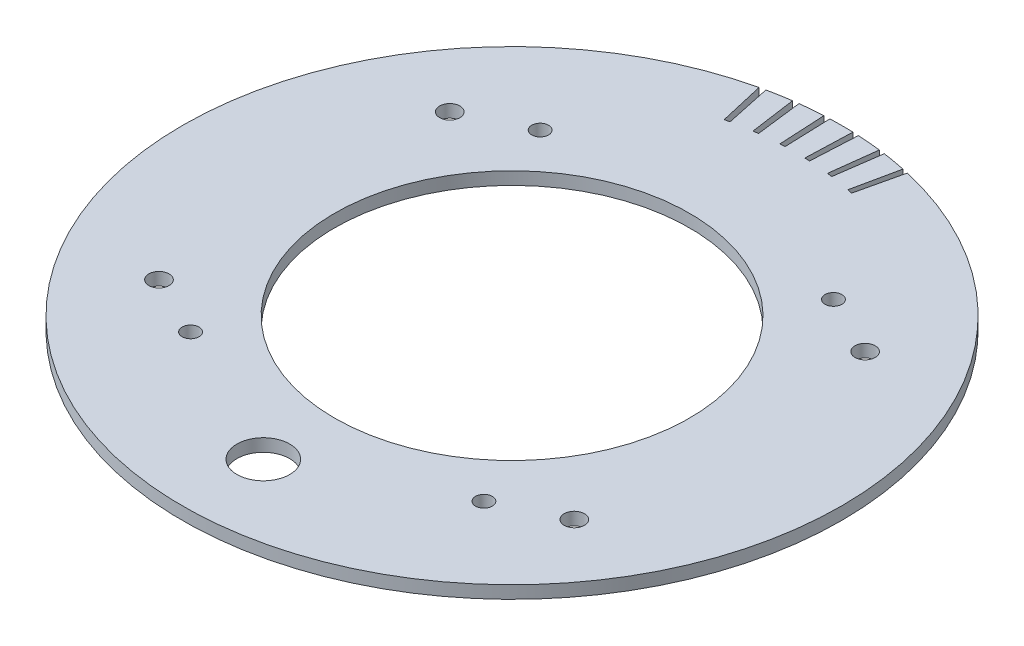
SolidWorks part; units mm, degrees
material "G10 Fiber Reinforced Plastic"
ref_plane "Front Plane" through (0, 0, 0) normal (0, 0, 1) x (1, 0, 0)
ref_plane "Top Plane" through (0, 0, 0) normal (0, 1, 0) x (1, 0, 0)
ref_plane "Right Plane" through (0, 0, 0) normal (1, 0, 0) x (0, 0, -1)
sketch "98mm - 6ID centering ring sketch" plane through (0, 0, 0) normal (0, 1, 0) x (1, 0, 0)
  line L0 (0, 0) -> (0, 50000) construction
  line L1 (0, 0) -> (50000, 0) construction
  line L2 (99.0091, 3.175) -> (56.4257, 3.175)
  line L3 (-99.0091, -3.175) -> (-56.4257, -3.175)
  line L4 (3.175, -99.0091) -> (3.175, -56.4257)
  line L5 (-3.175, 99.0091) -> (-3.175, 56.4257)
  line L7 (-56.4257, 3.175) -> (-99.0091, 3.175)
  line L8 (-3.175, -56.4257) -> (-3.175, -99.0091)
  line L9 (3.175, 56.4257) -> (3.175, 99.0091)
  line L11 (56.4257, -3.175) -> (99.0091, -3.175)
  circle A0 centre (0, 0) radius 99.06
  circle A1 centre (0, 0) radius 53.34
  arc A2 (-56.4257, 3.175) -> (-56.4257, -3.175) centre (0, 0) ccw
  arc A3 (-3.175, -56.4257) -> (3.175, -56.4257) centre (0, 0) ccw
  arc A4 (56.4257, -3.175) -> (56.4257, 3.175) centre (0, 0) ccw
  arc A5 (3.175, 56.4257) -> (-3.175, 56.4257) centre (0, 0) ccw
  dimension "D1" = 45.72
  dimension "D2" = 106.68
  dimension "D5" = 3.175
  dimension "D3" = 6.35
  dimension "D4" = 6.35
  dimension "D6" = 6.35
extrude "Centering Ring Extrude" add sketch "98mm - 6ID centering ring sketch" along normal blind 1.905 and the other way blind 1.905 contours L9 A5 L5 A0 L7 A2 L3 L8 A3 L4 L11 A4 L2 A1 | A4 L11 A0 L2 | A5 L9 A0 L5 | A2 L7 A0 L3 | A3 L8 A0 L4 region at (77.7641, 0, 0) region at (77.7174, 0, -5.9754) region at (0, 0, -77.7641) region at (0, 0, 77.7641) region at (-77.7641, 0, 0)
sketch "Sketch1" plane through (0, -1.905, 0) normal (0, -1, 0) x (1, 0, 0)
  line L0 (0, 0) -> (14.5226, 68.3236) construction
  line L1 (0, 0) -> (32.7926, -61.6739)
  line L2 (0, 0) -> (-55.0426, -43.004)
  line L3 (0, 0) -> (0, 69.85) construction
  circle A0 centre (0, 0) radius 69.85 construction
  circle A1 centre (32.7926, -61.6739) radius 3.175
  circle A2 centre (-55.0426, -43.004) radius 3.175
  dimension "D1" = 139.7
  dimension "D2" = 6.35
  dimension "D3" = 140
  dimension "D4" = 12
sketch "Sketch3" plane through (0, 1.905, 0) normal (0, 1, 0) x (1, 0, 0)
  line L0 (0, 0) -> (0, 99.06) construction
  line L1 (0, 0) -> (-22.2837, 96.5211)
  line L2 (0, 0) -> (-20.5957, 96.8953)
  circle A0 centre (0, 0) radius 99.06 construction
  circle A1 centre (0, 0) radius 99.06
  circle A2 centre (0, 0) radius 85.09
  circle M8 centre (0, 0) radius 99.06
  dimension "D1" = 13.97
  dimension "D2" = 12
  dimension "D3" = 1
extrude "Cut-Extrude3" cut sketch "Sketch3" against normal through all contours A2 L2 L1 M8 region at (-19.9667, 1.905, -90.0638)
pattern_circular "CirPattern1" count 6 every 5 about axis through (0, 1.905, 0) along (0, 1, 0) of "Cut-Extrude3" reverse direction yes
sketch "Sketch4" plane through (0, 1.905, 0) normal (0, 1, 0) x (1, 0, 0)
  line L0 (0, 0) -> (76.2, 0) construction
  line L1 (69.0607, 32.2035) -> (0, 0) construction
  line L2 (-75.0424, 13.232) -> (0, 0) construction
  line L3 (-58.3726, -48.9804) -> (0, 0) construction
  line L4 (0, 0) -> (65.9911, -38.1) construction
  circle A0 centre (0, 0) radius 76.2 construction
  circle A1 centre (69.0607, 32.2035) radius 3
  circle A2 centre (-75.0424, 13.232) radius 3
  circle A3 centre (65.9911, -38.1) radius 3
  circle A4 centre (-58.3726, -48.9804) radius 3
  dimension "D1" = 152.4
  dimension "D2" = 6
  dimension "D3" = 335
  dimension "D4" = 190
  dimension "D5" = 330
  dimension "D6" = 140
sketch "Sketch5" plane through (0, -1.905, 0) normal (0, -1, 0) x (1, 0, 0)
  line L0 (0, 0) -> (0, -99.06) construction
  line L1 (0, 0) -> (99.06, 0) construction
  line L2 (44.0824, 52.5353) -> (-44.0824, 52.5353) construction
  line L3 (-44.0824, 52.5353) -> (-44.0824, -52.5353) construction
  line L4 (-44.0824, -52.5353) -> (44.0824, -52.5353) construction
  line L5 (44.0824, -52.5353) -> (44.0824, 52.5353) construction
  line L6 (62.4194, 43.7065) -> (-62.4194, 43.7065) construction
  line L7 (-62.4194, 43.7065) -> (-62.4194, -43.7065) construction
  line L8 (-62.4194, -43.7065) -> (62.4194, -43.7065) construction
  line L9 (62.4194, -43.7065) -> (62.4194, 43.7065) construction
  line L10 (-44.0824, 52.5353) -> (44.0824, -52.5353) construction
  line L11 (44.0824, 52.5353) -> (-44.0824, -52.5353) construction
  line L12 (-62.4194, 43.7065) -> (62.4194, -43.7065) construction
  line L13 (62.4194, 43.7065) -> (-62.4194, -43.7065) construction
  line L14 (0, 74.7547) -> (0, 0) construction
  arc A0 (-3.4571, -98.9997) -> (3.4571, -98.9997) centre (0, 0) ccw construction
  circle A1 centre (-62.4194, 43.7065) radius 3.048
  circle A2 centre (-44.0824, 52.5353) radius 2.54
  circle A3 centre (44.0824, 52.5353) radius 2.54
  circle A4 centre (62.4194, 43.7065) radius 3.048
  circle A5 centre (62.4194, -43.7065) radius 3.048
  circle A6 centre (44.0824, -52.5353) radius 2.54
  circle A7 centre (-44.0824, -52.5353) radius 2.54
  circle A8 centre (-62.4194, -43.7065) radius 3.048
  arc A9 (22.2837, -96.5211) -> (-22.2837, -96.5211) centre (0, 0) ccw construction
  circle A10 centre (0, 74.7547) radius 7.9375
  point P24 (0, 0)
  point P25 (0, 0)
  dimension "D2" = 5.08
  dimension "D3" = 5.08
  dimension "D4" = 5.08
  dimension "D5" = 5.08
  dimension "D6" = 6.096
  dimension "D7" = 6.096
  dimension "D8" = 6.096
  dimension "D9" = 6.096
  dimension "D16" = 15.875
  dimension "D10" = 88.1647
  dimension "D11" = 105.0707
  dimension "D12" = 124.8388
  dimension "D13" = 87.413
  dimension "D14" = 90
  dimension "D15" = 74.7547
extrude "Cut-Extrude4" cut sketch "Sketch5" against normal up to surface (3.81 mm away) up to face at (0, 1.905, 53.34)
